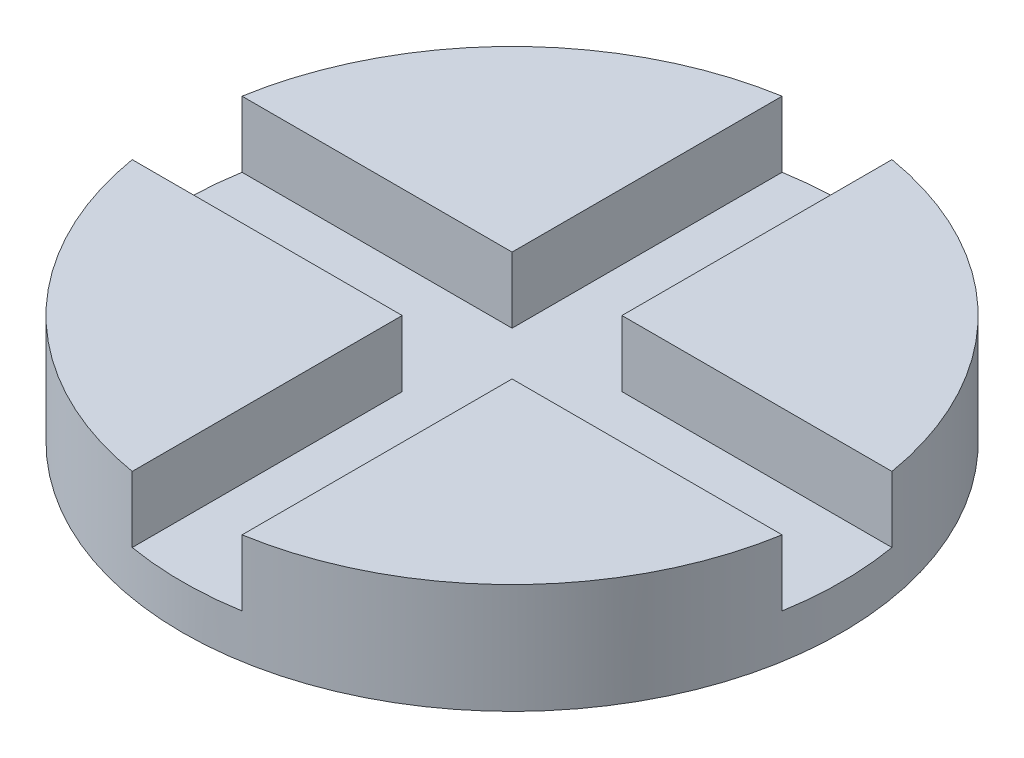
SolidWorks part; units mm, degrees
ref_plane "Front Plane" through (0, 0, 0) normal (0, 0, 1) x (1, 0, 0)
ref_plane "Top Plane" through (0, 0, 0) normal (0, 1, 0) x (1, 0, 0)
ref_plane "Right Plane" through (0, 0, 0) normal (1, 0, 0) x (0, 0, -1)
sketch "Sketch1" plane through (0, 0, 0) normal (0, 1, 0) x (1, 0, 0)
  line L0 (-10, 10) -> (-10, 59.1608)
  line L1 (-10, 10) -> (-59.1608, 10)
  line L2 (10, -59.1608) -> (10, -10)
  line L3 (10, 10) -> (10, 59.1608)
  line L4 (-10, -59.1608) -> (-10, -10)
  line L5 (10, -59.1608) -> (-10, 59.1608) construction
  line L6 (10, 59.1608) -> (-10, -59.1608) construction
  line L7 (59.1608, 10) -> (10, 10)
  line L8 (-10, -10) -> (-59.1608, -10)
  line L9 (59.1608, -10) -> (10, -10)
  line L11 (59.1608, 10) -> (-59.1608, -10) construction
  line L12 (59.1608, -10) -> (-59.1608, 10) construction
  circle A0 centre (0, 0) radius 60
  dimension "D1" = 120
  dimension "D2" = 20
  dimension "D3" = 20
extrude "Boss-Extrude1" add sketch "Sketch1" along normal blind 20 contours L0 A0 L1 | L9 A0 L7 L3 L0 L1 L8 L4 L2 | L8 A0 L4 | L7 A0 L3 | L2 A0 L9 region at (-29.8253, 0, -29.8253) region at (0, 0, 0) region at (29.8253, 0, -29.8253) region at (-29.8253, 0, 29.8253) region at (29.8253, 0, 29.8253)
extrude "Cut-Extrude1" cut sketch "Sketch1<3>" against normal blind 12 from surface contours L9 A0 L7 L3 L0 L1 L8 L4 L2 region at (0, 0, 0) starting at face at (0, 20, 60)
sketch "Sketch1<3>" plane through (0, 0, 0) normal (0, 1, 0) x (1, 0, 0) same geometry as "Sketch1"
